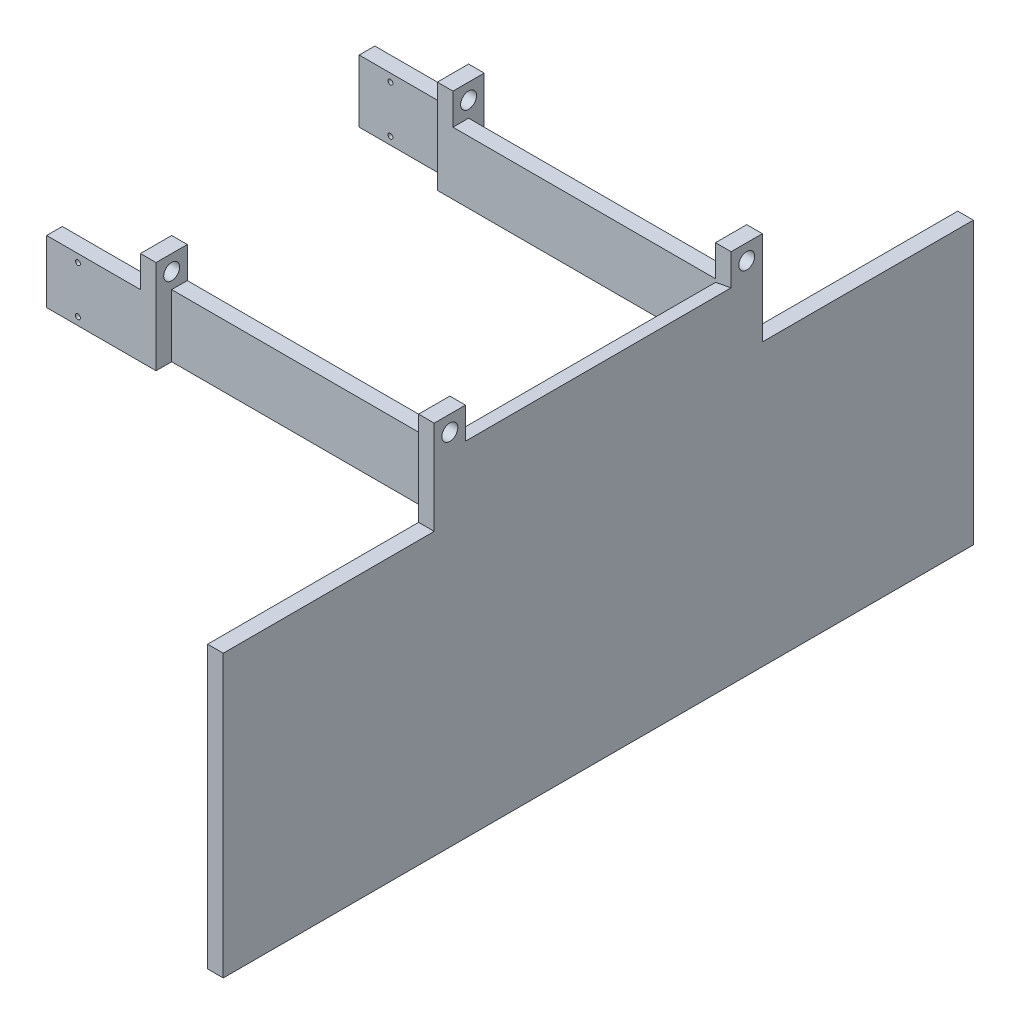
SolidWorks part; units mm, degrees
ref_plane "Front Plane" through (0, 0, 0) normal (0, 0, 1) x (1, 0, 0)
ref_plane "Top Plane" through (0, 0, 0) normal (0, 1, 0) x (1, 0, 0)
ref_plane "Right Plane" through (0, 0, 0) normal (1, 0, 0) x (0, 0, -1)
sketch "Sketch1" plane through (0, 0, 0) normal (0, 1, 0) x (1, 0, 0)
  line L0 (3.175, 114.3) -> (0, 114.3)
  line L1 (0, 0) -> (119.38, 0)
  line L2 (0, 0) -> (0, 6.35)
  line L3 (0, 120.65) -> (119.38, 120.65)
  line L4 (119.38, 0) -> (119.38, 120.65)
  line L5 (3.175, 114.3) -> (113.03, 114.3)
  line L7 (3.175, 6.35) -> (113.03, 6.35)
  line L8 (113.03, 114.3) -> (113.03, 6.35)
  line L9 (3.175, 6.35) -> (0, 6.35)
  line L10 (0, 114.3) -> (0, 120.65)
  dimension "D1" = 120.65
  dimension "D2" = 113.03
  dimension "D3" = 6.35
  dimension "D5" = 6.35
  dimension "D6" = 107.95
extrude "Boss-Extrude1" add sketch "Sketch1" along normal blind 25.4
sketch "Sketch2" plane through (0, 0, 0) normal (0, 0, 1) x (1, 0, 0)
  line L0 (119.38, 25.4) -> (113.03, 24.13)
  line L1 (113.03, 24.13) -> (113.03, 25.4)
  line L2 (0, 25.4) -> (119.38, 25.4) construction
  line L4 (113.03, 25.4) -> (119.38, 25.4)
  dimension "D2" = 1.27
extrude "Cut-Extrude1" cut sketch "Sketch2" against normal up to surface (114.3 mm away) from surface up to face at (56.515, 12.7, -114.3) starting at face at (56.515, 12.7, -6.35)
sketch "Sketch3" plane through (0, 0, 0) normal (0, 0, 1) x (1, 0, 0)
  line L0 (0, 25.4) -> (119.38, 25.4) construction
  line L1 (6.35, 25.4) -> (-38.1, 25.4)
  line L2 (6.35, 25.4) -> (6.35, 0)
  line L3 (6.35, 0) -> (-38.1, 0)
  line L4 (-38.1, 25.4) -> (-38.1, 0)
  line L5 (0, 25.4) -> (0, 0) construction
  dimension "D1" = 6.35
  dimension "D2" = 38.1
extrude "Boss-Extrude2" add sketch "Sketch3" along normal blind 6.35
extrude "Boss-Extrude3" add sketch "Sketch3<2>" against normal blind 6.35 from surface starting at face at (59.69, 12.7, -120.65)
sketch "Sketch3<2>" plane through (0, 0, 0) normal (0, 0, 1) x (1, 0, 0) same geometry as "Sketch3"
sketch "Sketch4" plane through (0, 0, 0) normal (0, -1, 0) x (1, 0, 0)
  line L1 (119.38, 92.075) -> (113.03, 92.075)
  line L2 (119.38, 92.075) -> (119.38, -212.725)
  line L3 (119.38, -212.725) -> (113.03, -212.725)
  line L4 (113.03, 92.075) -> (113.03, -212.725)
  line L6 (119.38, 0) -> (119.38, -120.65) construction
  line L7 (113.03, -114.3) -> (113.03, -6.35) construction
  point P10 (113.03, -60.325)
  point P11 (113.03, -60.325)
  dimension "D1" = 304.8
extrude "Boss-Extrude4" add sketch "Sketch4" along normal blind 114.3
sketch "Sketch8" plane through (0, 25.4, 0) normal (0, 1, 0) x (1, 0, 0)
  line L0 (119.38, 60.325) -> (-5.0576, 60.325) construction
  line L1 (119.38, -6.35) -> (113.03, -6.35)
  line L2 (119.38, -6.35) -> (119.38, 6.35)
  line L4 (113.03, -6.35) -> (113.03, 6.35)
  line L5 (113.03, 6.35) -> (119.38, 6.35)
  line L6 (59.69, 114.3) -> (59.69, -20.9935) construction
  line L7 (0, 114.3) -> (119.38, 114.3) construction
  line L8 (119.38, 114.3) -> (119.38, 6.35) construction
  line L9 (6.35, -6.35) -> (6.35, 6.35)
  line L10 (0, 6.35) -> (6.35, 6.35)
  line L11 (0, -6.35) -> (0, 6.35)
  line L12 (0, -6.35) -> (6.35, -6.35)
  line L22 (0, 127) -> (6.35, 127)
  line L23 (0, 127) -> (0, 114.3)
  line L24 (0, 114.3) -> (6.35, 114.3)
  line L25 (6.35, 127) -> (6.35, 114.3)
  line L26 (113.03, 127) -> (113.03, 114.3)
  line L27 (119.38, 114.3) -> (113.03, 114.3)
  line L28 (119.38, 127) -> (119.38, 114.3)
  line L29 (119.38, 127) -> (113.03, 127)
  dimension "D1" = 12.7
extrude "Boss-Extrude7" add sketch "Sketch8" against normal up to surface (25.4 mm away) from offset 12.7 up to face at (116.205, 0, 46.0375)
sketch "Sketch9" plane through (6.35, 0, 0) normal (1, 0, 0) x (0, 0, -1)
  line L1 (-6.35, 38.1) -> (6.35, 38.1) construction
  line L2 (-6.35, 38.1) -> (-6.35, 0) construction
  line L3 (60.325, 36.7762) -> (60.325, 19.9574) construction
  line L4 (6.35, 38.1) -> (6.35, 0) construction
  circle A0 centre (0, 31.75) radius 3.2385
  circle A1 centre (120.65, 31.75) radius 3.2385
  dimension "D1" = 6.477
  dimension "D3" = 6.35
  dimension "D4" = 53.975
  dimension "D2" = 6.35
extrude "Cut-Extrude2" cut sketch "Sketch9" against normal through all both and the other way through all
sketch "Sketch10" plane through (0, 0, 6.35) normal (0, 0, 1) x (1, 0, 0)
  line L0 (0, 25.4) -> (-38.1, 25.4) construction
  line L1 (-38.1, 25.4) -> (-38.1, 0) construction
  circle A0 centre (-25.4, 22.225) radius 1
  circle A1 centre (-25.4, 3.175) radius 1
  dimension "D2" = 2
  dimension "D4" = 2
  dimension "D1" = 3.175
  dimension "D3" = 12.7
  dimension "D5" = 19.05
  dimension "D6" = 12.7
extrude "Cut-Extrude3" cut sketch "Sketch10" against normal through all
equation "\"tightTol\" = 0.005in"
equation "\"normTol\"= 0.01in"
equation "\"looseTol\"= 0.02in"
equation "\"D1@Sketch9\"=\"tightTol\"+0.250000in"
equation "\"D2@Sketch10\"=2mm"
equation "\"D4@Sketch10\"=2mm"
